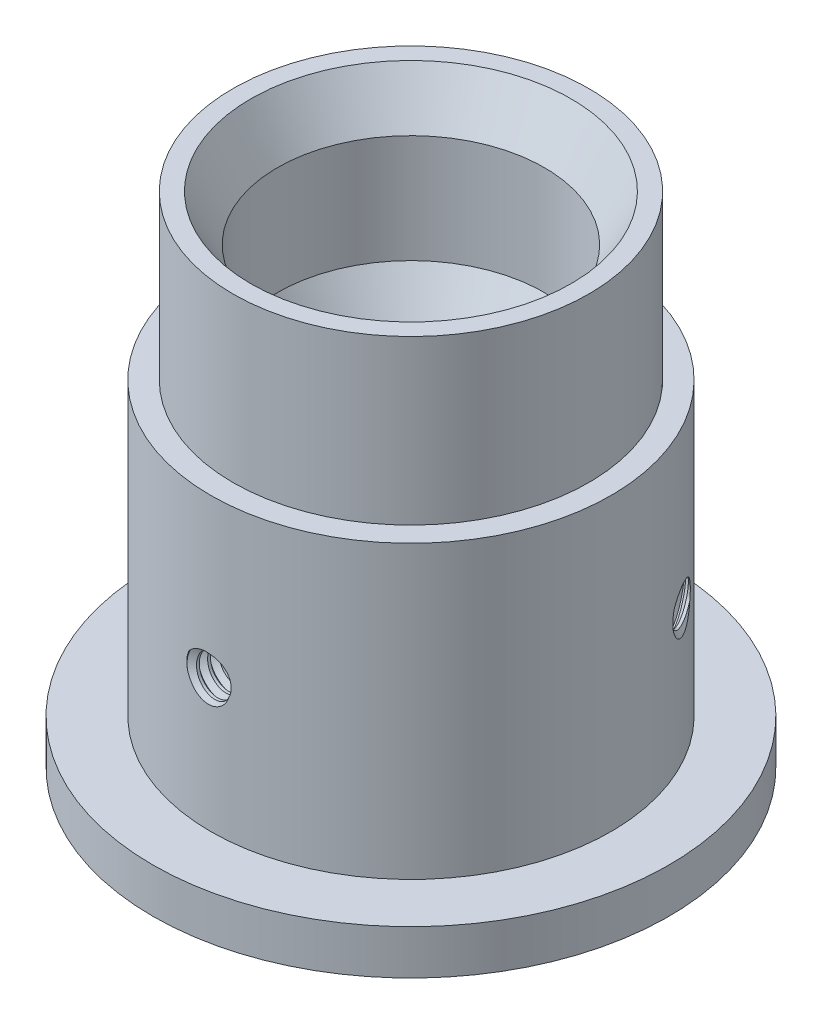
SolidWorks part; units mm, degrees
material "6061-T6 (SS)"
ref_plane "Front Plane" through (0, 0, 0) normal (0, 0, 1) x (1, 0, 0)
ref_plane "Top Plane" through (0, 0, 0) normal (0, 1, 0) x (1, 0, 0)
ref_plane "Right Plane" through (0, 0, 0) normal (1, 0, 0) x (0, 0, -1)
sketch "Sketch1" plane through (0, 0, 0) normal (0, 0, 1) x (1, 0, 0)
  line L0 (7.3025, -2.6215) -> (7.3025, -21.3837)
  line L1 (7.3025, -21.3837) -> (5.9123, -21.3837)
  line L2 (5.9123, -21.3837) -> (6.6247, -24.7354)
  line L3 (6.6247, -24.7354) -> (11.8181, -24.7354)
  line L4 (18.415, -23.356) -> (18.415, -20.181)
  line L5 (18.415, -20.181) -> (14.2875, -20.181)
  line L6 (14.2875, -20.181) -> (14.2875, 0.594)
  line L8 (9.525, 1.228) -> (7.3025, -2.6215)
  line L9 (0, 0) -> (0, -50000) construction
  line L10 (14.2875, 0.594) -> (12.7, 0.594)
  line L11 (12.7, 0.594) -> (12.7, 12.2485)
  line L12 (11.43, 12.2485) -> (9.525, 8.949)
  line L13 (9.525, 8.949) -> (9.525, 1.228)
  line L14 (9.525, 8.949) -> (3.3907, -1.6759) construction
  line L15 (2.6788, -6.1711) -> (5.9123, -21.3837) construction
  line L16 (2.54, -3.9263) -> (2.54, 49996.0737) construction
  line L17 (11.8181, -24.7354) -> (11.8181, -23.356)
  line L18 (11.8181, -23.356) -> (18.415, -23.356)
  line L19 (12.7, 12.2485) -> (11.43, 12.2485)
  arc A0 (3.3907, -1.6759) -> (2.6788, -6.1711) centre (8.89, -4.8509) ccw construction
  point P18 (2.54, -4.8509)
  dimension "D8" = 6.35
  dimension "D1" = 5.08
  dimension "D2" = 14.2875
  dimension "D3" = 18.415
  dimension "D4" = 12
  dimension "D5" = 3.175
  dimension "D6" = 6.985
  dimension "D7" = 1.5875
  dimension "D9" = 30
  dimension "D10" = 13.2495
  dimension "D11" = 1.27
  dimension "D12" = 3.175
revolve "Revolve1" add sketch "Sketch1" angle 360 about L9
sketch "Sketch2" plane through (0, 0, 0) normal (0, 0, 1) x (1, 0, 0)
  line L0 (18.415, -20.181) -> (-18.415, -20.181) construction
  circle A0 centre (0, -10.656) radius 1.397
  point P4 (0, 0)
  dimension "D1" = 2.794
  dimension "D2" = 9.525
extrude "Cut-Extrude1" cut sketch "Sketch2" along normal through all
ref_plane "Plane1" through (0, 0, 14.2875) normal (0, 0, 1) x (1, 0, 0)
sketch "Sketch3" plane through (0, 0, 14.2875) normal (0, 0, 1) x (1, 0, 0)
  circle A0 centre (0, -10.656) radius 1.397 construction
  circle A1 centre (0, -10.656) radius 1.397
  point P0 (0, -10.656)
  point P8 (0, -9.259)
ref_point "Point1"
thread "Thread1" pitch 0.7937 method cut profile "Thread Profile1" start angle 0, offset 1, length 0, pitch 0.7937, diameter 2.794
ref_plane "Plane2" through (-1.397, -10.656, 15.2875) normal (0, -1, 0) x (-1, 0, 0)
sketch "Thread Profile1" plane through (-1.397, -10.656, 15.2875) normal (0, -1, 0) x (-1, 0, 0)
  line L0 (0, 0) -> (0, 0.7937) construction
  line L1 (0, 0) -> (0.4296, 0.248)
  line L2 (0.4296, 0.248) -> (0.4296, 0.3473)
  line L3 (0.4296, 0.3473) -> (0, 0.5953)
  line L4 (0.4296, 0.2977) -> (0, 0.2977) construction
  line L11 (0, 0) -> (0, 0.5953)
  point P2 (0, 0)
  dimension "Pitch" = 0.7937
  dimension "Profile_Angle" = 60
  dimension "Profile_Land" = 0.0992
  dimension "Profile_Height" = 0.4296
pattern_circular "CirPattern2" count 3 over 360 about axis through (0, 0, 0) along (0, 1, 0) of "Cut-Extrude1", "Thread1" reverse direction yes
